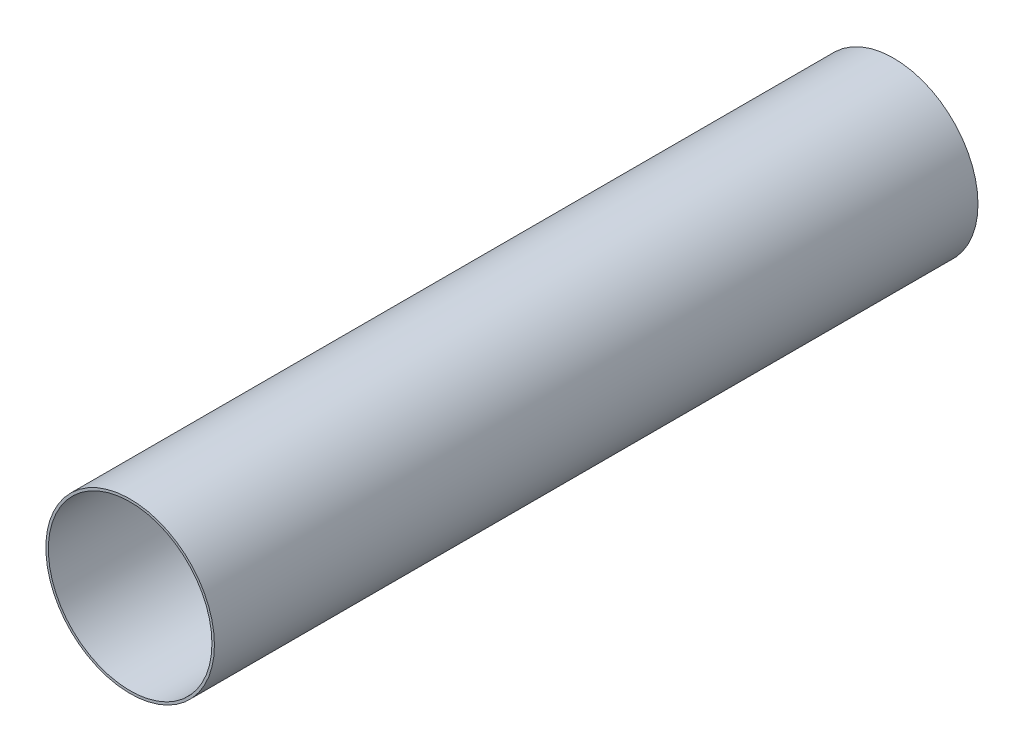
SolidWorks part; units mm, degrees
ref_plane "Front Plane" through (0, 0, 0) normal (0, 0, 1) x (1, 0, 0)
ref_plane "Top Plane" through (0, 0, 0) normal (0, 1, 0) x (1, 0, 0)
ref_plane "Right Plane" through (0, 0, 0) normal (1, 0, 0) x (0, 0, -1)
sketch "Sketch1" plane through (0, 0, 0) normal (0, 0, 1) x (1, 0, 0)
  circle A0 centre (0, 0) radius 39.2557
  circle A1 centre (0, 0) radius 38.1
  dimension "D1" = 76.2
  dimension "D2" = 78.5114
extrude "Boss-Extrude1" add sketch "Sketch1" along normal mid plane 355.6
equation "\"AIRFRAME_OD\"= 5.15in"
equation "\"AIRFRAME_ID\"= 5.00in"
equation "\"FLAT_T\"= 0.125in"
equation "\"NOSE_EXP_L\"= 27in"
equation "\"NOSE_SHOULDER_L\"= 5in"
equation "\"MAIN_L\"= 30in"
equation "\"RECO_COUP_L\"= 10in"
equation "\"RECO_SWITCH_L\"= 2in"
equation "\"DROGUE_L\"= 20in"
equation "\"ATS_FORE_COUP_L\"= 5.5in"
equation "\"ATS_AFT_COUP_L\"= 4.5in"
equation "\"LOWER_L\"= 30in"
equation "\"FIN_N\"= 4"
equation "\"CR_AFT_X\"= 0.5in"
equation "\"CR_FORE_X\"= 9.25in"
equation "\"D1@Sketch1\"=\"MOTOR_ID\""
equation "\"D2@Sketch1\"=\"MOTOR_OD\""
equation "\"D1@Boss-Extrude1\"=\"MOTOR_L\""
equation "\"FIN_ROOT\"= 8in"
equation "\"FIN_X\"= 0.75in"
equation "\"MOTOR_OD\"= 3.091in"
equation "\"MOTOR_ID\"= 3.00in"
equation "\"COUPLER_OD\"= 4.998in"
equation "\"COUPLER_ID\"= 4.88in"
equation "\"RECO_ROD_X\"= 3.5in"
equation "\"ATS_ROD_X\"= 3in"
equation "\"MOTOR_L\"= 14in"
equation "\"MOTOR_LOWER_X\"= 2in"
